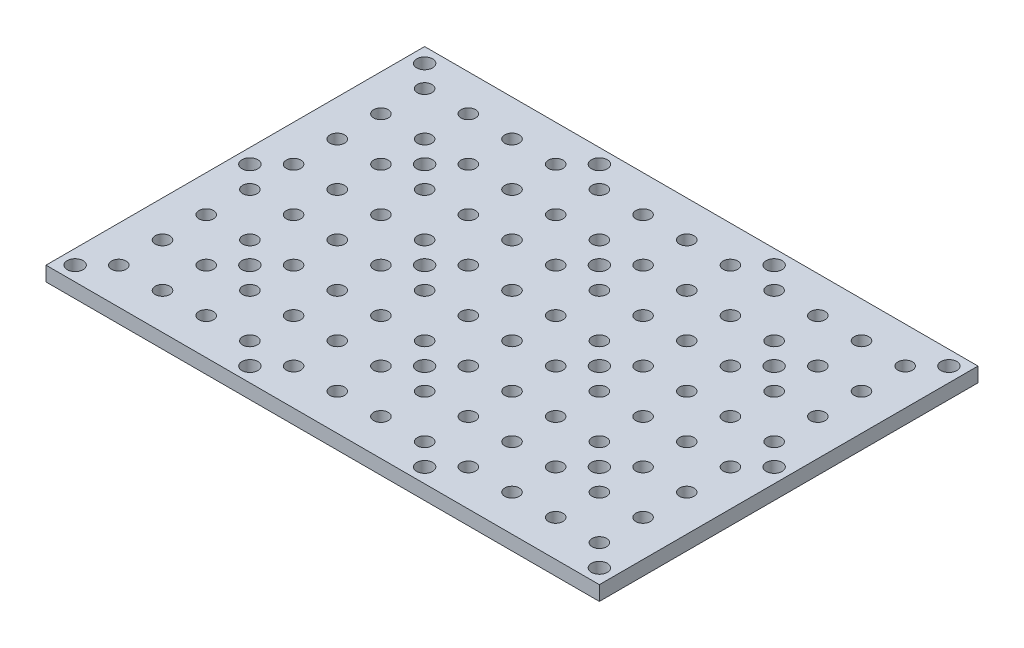
SolidWorks part; units mm, degrees
ref_plane "Front Plane" through (0, 0, 0) normal (0, 0, 1) x (1, 0, 0)
ref_plane "Top Plane" through (0, 0, 0) normal (0, 1, 0) x (1, 0, 0)
ref_plane "Right Plane" through (0, 0, 0) normal (1, 0, 0) x (0, 0, -1)
sketch "Sketch1" plane through (0, 0, 0) normal (0, 1, 0) x (1, 0, 0)
  line L1 (57, -39) -> (-57, -39)
  line L2 (57, -39) -> (57, 39)
  line L3 (57, 39) -> (-57, 39)
  line L4 (-57, -39) -> (-57, 39)
  line L5 (57, -39) -> (-57, 39) construction
  line L6 (57, 39) -> (-57, -39) construction
  point P0 (0, 0)
  dimension "D1" = 114
  dimension "D2" = 78
extrude "Boss-Extrude1" add sketch "Sketch1" along normal mid plane 3
sketch "Sketch2" plane through (0, 0, 0) normal (0, 1, 0) x (1, 0, 0)
  line L0 (0, -0.715) -> (0, 0.715) construction
  line L1 (-0.715, 0) -> (0.715, 0) construction
  circle A0 centre (-4.5, 4.5) radius 1.5
  dimension "D1" = 3
  dimension "D2" = 4.5
  dimension "D3" = 4.5
extrude "Cut-Extrude2" cut sketch "Sketch2" along normal through all and the other way through all
ref_axis "Axis1" through (-60.5, 0, 0) along (1, 0, 0)
ref_axis "Axis2" through (0, 0, 41.25) along (0, 0, -1)
pattern_linear "LPattern1" count 6 spacing 9 along (-1, 0, 0) count 4 spacing 9 along (0, 0, -1) of "Cut-Extrude2"
mirror "Mirror1" about plane through (0, 0, 0) normal (0, 0, 1) of "LPattern1", "Cut-Extrude2"
mirror "Mirror2" about plane through (0, 0, 0) normal (1, 0, 0) of "Cut-Extrude2", "Mirror1", "LPattern1"
hole_wizard "#4 Clearance Hole1" positions "Sketch3" profile "Sketch4" hole size "#4" standard "ANSI Inch" end condition through all
sketch "Sketch3" plane through (0, 1.5, 0) normal (0, 1, 0) x (1, 0, 0)
  line L1 (36, -18) -> (-36, -18) construction
  line L2 (36, -18) -> (36, 18) construction
  line L3 (36, 18) -> (-36, 18) construction
  line L4 (-36, -18) -> (-36, 18) construction
  line L5 (36, -18) -> (-36, 18) construction
  line L6 (36, 18) -> (-36, -18) construction
  line L7 (-1.65, 0) -> (1.65, 0) construction
  line L8 (0, -1.65) -> (0, 1.65) construction
  line L9 (-54, 36) -> (-18, 36) construction
  line L10 (-18, 36) -> (18, 36) construction
  line L11 (18, 36) -> (54, 36) construction
  line L12 (54, 36) -> (54, 0) construction
  line L13 (54, 0) -> (54, -36) construction
  line L14 (54, -36) -> (18, -36) construction
  line L15 (18, -36) -> (-18, -36) construction
  line L16 (-18, -36) -> (-54, -36) construction
  line L17 (-54, -36) -> (-54, 0) construction
  line L18 (-54, 0) -> (-54, 36) construction
  line L21 (-18, -36) -> (-18, 0) construction
  line L22 (-18, 0) -> (-18, 36) construction
  line L25 (18, -36) -> (18, 0) construction
  line L26 (18, 0) -> (18, 36) construction
  line L29 (54, 0) -> (18, 0) construction
  line L30 (18, 0) -> (-18, 0) construction
  line L31 (-18, 0) -> (-54, 0) construction
  line L33 (0, 0) -> (0, 36) construction
  point P2 (-36, 18)
  point P139 (36, -18)
  point P140 (36, 18)
  point P141 (-36, -18)
  point P149 (0, 18)
  point P151 (0, -18)
  point P152 (-54, 36)
  point P154 (-18, 36)
  point P156 (18, 36)
  point P158 (54, 36)
  point P160 (54, 0)
  point P162 (18, 0)
  point P164 (-18, 0)
  point P166 (-54, 0)
  point P168 (-54, -36)
  point P170 (-18, -36)
  point P172 (18, -36)
  point P174 (54, -36)
  point P226 (-52.8421, 0.0265)
  dimension "D1" = 18
  dimension "D2" = 36
  dimension "D3" = 36
  dimension "D4" = 18
  dimension "D5" = 54
sketch "Sketch4" plane through (-36, 1.5, -18) normal (1, 0, 0) x (0, 0, 1)
  line L0 (0, 0) -> (0, 3)
  line L1 (0, 3) -> (1.6319, 3)
  line L2 (1.6319, 3) -> (1.6319, 0)
  line L5 (1.6319, 0) -> (0, 0)
  line L11 (0, -6.35) -> (0, 107.95) construction
  dimension "Thru Hole Dia." = 3.2639
  dimension "Thru Hole Depth" = 3
